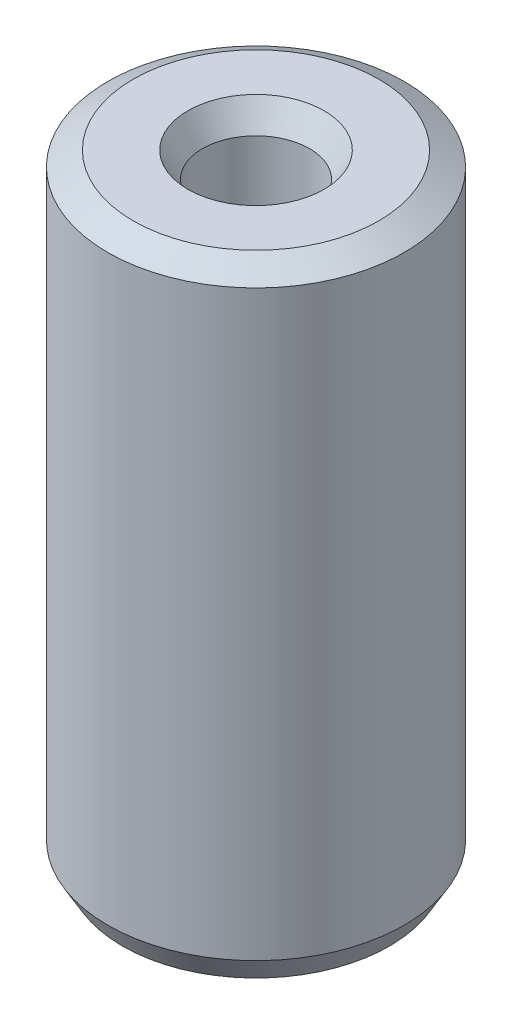
SolidWorks part; units mm, degrees
ref_plane "Front Plane" through (0, 0, 0) normal (0, 0, 1) x (1, 0, 0)
ref_plane "Top Plane" through (0, 0, 0) normal (0, 1, 0) x (1, 0, 0)
ref_plane "Right Plane" through (0, 0, 0) normal (1, 0, 0) x (0, 0, -1)
sketch "Sketch1" plane through (0, 0, 0) normal (0, 1, 0) x (1, 0, 0)
  circle A0 centre (0, 0) radius 12.5
  dimension "SLEEVE_OD" = 25
extrude "Boss-Extrude1" add sketch "Sketch1" along normal blind 52.5242
sketch "Sketch2" plane through (0, 0, 0) normal (0, 1, 0) x (1, 0, 0)
  circle A0 centre (0, 0) radius 4.5084
  dimension "BORE_D" = 9.0168
extrude "Cut-Extrude1" cut sketch "Sketch2" along normal through all
chamfer "Chamfer1" distance 1.2385 angle 60 4 edges at (0, 52.5242, 4.5084) (0, 0, 4.5084) (0, 0, 12.5) (0, 52.5242, 12.5) first distance on face at (0, 52.5242, 4.5084) first distance on face at (0, 0, 4.5084) first distance on face at (0, 52.5242, 12.5)
